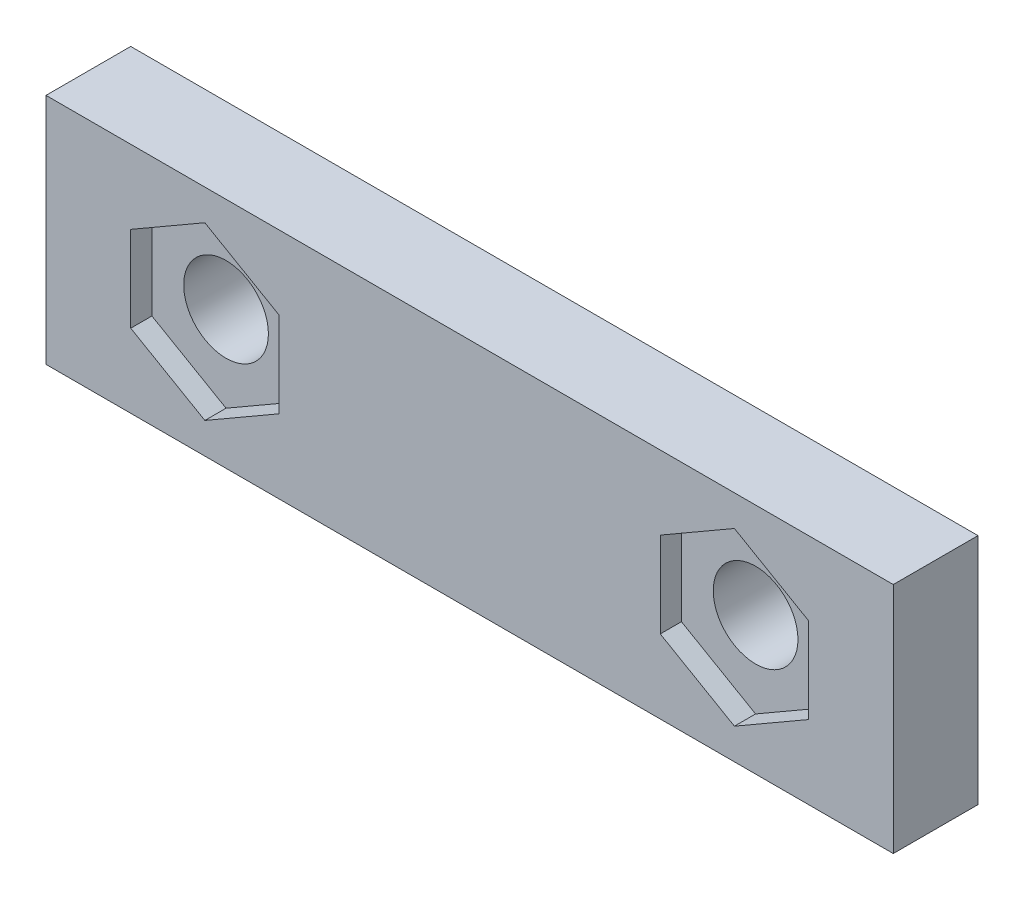
SolidWorks part; units mm, degrees
material "ABS"
ref_plane "Front Plane" through (0, 0, 0) normal (0, 0, 1) x (1, 0, 0)
ref_plane "Top Plane" through (0, 0, 0) normal (0, 1, 0) x (1, 0, 0)
ref_plane "Right Plane" through (0, 0, 0) normal (1, 0, 0) x (0, 0, -1)
sketch "Sketch1" plane through (0, 0, 0) normal (0, 0, 1) x (1, 0, 0)
  line L0 (189.6, -50.5) -> (240, -50.5) construction
  line L1 (234.8, -39.5) -> (194.8, -39.5)
  line L2 (234.8, -39.5) -> (234.8, -50.5)
  line L3 (234.8, -50.5) -> (194.8, -50.5)
  line L4 (194.8, -39.5) -> (194.8, -50.5)
  line L5 (234.8, -39.5) -> (194.8, -50.5) construction
  line L6 (234.8, -50.5) -> (194.8, -39.5) construction
  line L8 (227.3, -49.0415) -> (230.8, -47.0207)
  line L9 (230.8, -47.0207) -> (230.8, -42.9793)
  line L10 (230.8, -42.9793) -> (227.3, -40.9585)
  line L11 (227.3, -40.9585) -> (223.8, -42.9793)
  line L12 (223.8, -42.9793) -> (223.8, -47.0207)
  line L13 (223.8, -47.0207) -> (227.3, -49.0415)
  line L14 (202.3, -49.0415) -> (205.8, -47.0207)
  line L15 (205.8, -47.0207) -> (205.8, -42.9793)
  line L16 (205.8, -42.9793) -> (202.3, -40.9585)
  line L17 (202.3, -40.9585) -> (198.8, -42.9793)
  line L18 (198.8, -42.9793) -> (198.8, -47.0207)
  line L19 (198.8, -47.0207) -> (202.3, -49.0415)
  circle A0 centre (227.3, -45) radius 2
  circle A1 centre (202.3, -45) radius 2
  circle A2 centre (227.3, -45) radius 3.5 construction
  circle A3 centre (202.3, -45) radius 3.5 construction
  point P4 (214.8, -45)
  point P13 (200.55, -41.9689)
  dimension "D4" = 4
  dimension "D5" = 4
  dimension "D1" = 5.5
  dimension "D2" = 40
  dimension "D3" = 7.5
  dimension "D6" = 7
  dimension "D7" = 7
extrude "Boss-Extrude1" add sketch "Sketch1" along normal blind 3 contours L1 L4 L3 L2 L19 L18 L17 L16 L15 L14 L13 L12 L11 L10 L9 L8 | L18 L19 L14 L15 L16 L17 A1 | L12 L13 L8 L9 L10 L11 A0 region at (214.8, -45, 0) region at (225.6035, -47.9385, 0) region at (200.6035, -47.9385, 0)
extrude "Boss-Extrude2" add sketch "Sketch1<3>" along normal blind 4 contours L1 L4 L3 L2 L19 L18 L17 L16 L15 L14 L13 L12 L11 L10 L9 L8 region at (214.8, -45, 0)
sketch "Sketch1<3>" plane through (0, 0, 0) normal (0, 0, 1) x (1, 0, 0) same geometry as "Sketch1"
